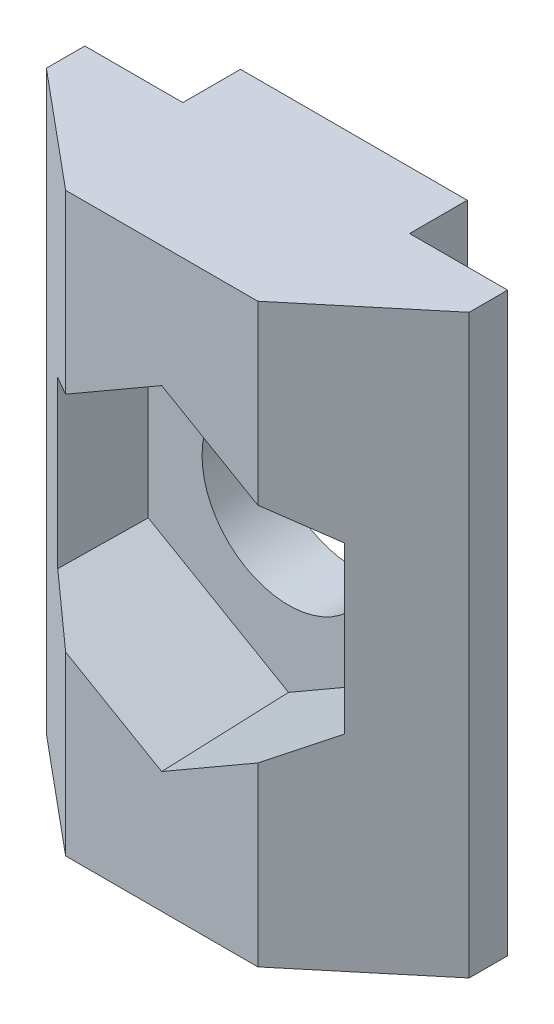
SolidWorks part; units mm, degrees
material "ABS"
ref_plane "Front Plane" through (0, 0, 0) normal (0, 0, 1) x (1, 0, 0)
ref_plane "Top Plane" through (0, 0, 0) normal (0, 1, 0) x (1, 0, 0)
ref_plane "Right Plane" through (0, 0, 0) normal (1, 0, 0) x (0, 0, -1)
sketch "Sketch1" plane through (0, 0, 0) normal (0, 1, 0) x (1, 0, 0)
  line L0 (-2.95, 0) -> (2.95, 0)
  line L1 (2.95, 0) -> (2.95, -1.5)
  line L2 (2.95, -1.5) -> (5.5, -1.5)
  line L3 (5.5, -1.5) -> (5.5, -2.5)
  line L4 (5.5, -2.5) -> (2.5, -5)
  line L5 (2.5, -5) -> (-2.5, -5)
  line L6 (-2.5, -5) -> (-5.5, -2.5)
  line L7 (-5.5, -2.5) -> (-5.5, -1.5)
  line L8 (-5.5, -1.5) -> (-2.95, -1.5)
  line L9 (-2.95, -1.5) -> (-2.95, 0)
  line L10 (0, 0) -> (0, -5) construction
  dimension "D1" = 5.9
  dimension "D2" = 5
  dimension "D3" = 1
  dimension "D4" = 2.55
  dimension "D5" = 1.5
  dimension "D6" = 5
extrude "Boss-Extrude1" add sketch "Sketch1" along normal mid plane 15
sketch "Sketch2" plane through (0, 0, 5) normal (0, 0, 1) x (1, 0, 0)
  circle A0 centre (0, 0) radius 2.25
  dimension "D1" = 4.5
extrude "Cut-Extrude1" cut sketch "Sketch2" against normal through all
sketch "Sketch3" plane through (0, 0, 5) normal (0, 0, 1) x (1, 0, 0)
  line L1 (0, 4.2147) -> (-3.65, 2.1073)
  line L2 (-3.65, 2.1073) -> (-3.65, -2.1073)
  line L3 (-3.65, -2.1073) -> (0, -4.2147)
  line L4 (0, -4.2147) -> (3.65, -2.1073)
  line L5 (3.65, -2.1073) -> (3.65, 2.1073)
  line L6 (3.65, 2.1073) -> (0, 4.2147)
  circle A0 centre (0, 0) radius 3.65 construction
  dimension "D1" = 7.3
extrude "Cut-Extrude2" cut sketch "Sketch3" along normal through all draft 2 from offset 3.3 draft outward yes offset against normal yes
